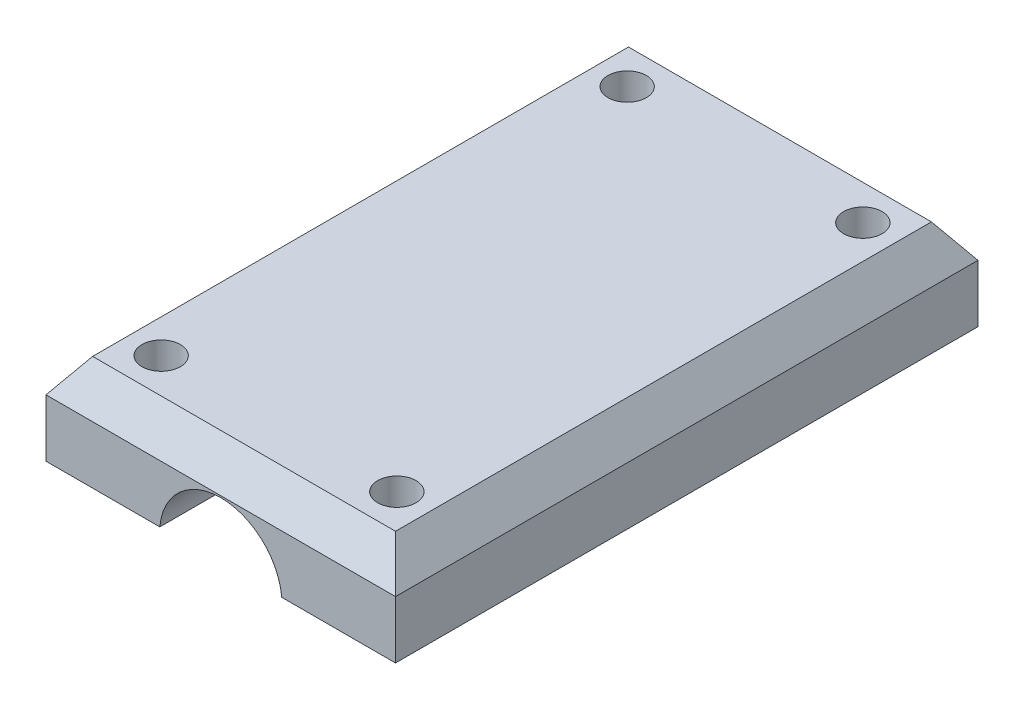
SolidWorks part; units mm, degrees
ref_plane "Front Plane" through (0, 0, 0) normal (0, 0, 1) x (1, 0, 0)
ref_plane "Top Plane" through (0, 0, 0) normal (0, 1, 0) x (1, 0, 0)
ref_plane "Right Plane" through (0, 0, 0) normal (1, 0, 0) x (0, 0, -1)
sketch "Sketch2" plane through (0, 0, 0) normal (0, 0, 1) x (1, 0, 0)
  line L0 (15, 0) -> (5.23, 0) construction
  line L1 (5.23, 0) -> (15, 0)
  line L2 (-5.23, 0) -> (-15, 0)
  line L3 (-15, 0) -> (-15, 7.7924)
  line L4 (-15, 7.7924) -> (15, 7.7924)
  line L5 (15, 7.7924) -> (15, 0)
  line L6 (-15, 4.7924) -> (15, 4.7924) construction
  arc A0 (-5.23, 0) -> (5.23, 0) centre (0, 0.4576) ccw construction
  arc A1 (-5.23, 0) -> (5.23, 0) centre (0, 0.4576) ccw construction
  arc A2 (-5.23, 0) -> (5.23, 0) centre (0, -0.4576) cw
  dimension "D1" = 3
extrude "Boss-Extrude1" add sketch "Sketch2" against normal up to surface (50 mm away)
sketch "Sketch3" plane through (0, 0, -50) normal (0, 0, -1) x (-1, 0, 0)
  line L0 (0, -4.5958) -> (0, 4.5958)
sketch "Sketch4" plane through (0, 7.7924, 0) normal (0, 1, 0) x (1, 0, 0)
  line L0 (-10.115, 45) -> (-10.115, 5) construction
  circle A0 centre (-10.115, 45) radius 1.65
  circle A1 centre (-10.115, 5) radius 1.65
  circle A2 centre (10.115, 45) radius 1.65
  circle A3 centre (10.115, 5) radius 1.65
  dimension "D1" = 3.3
  dimension "D2" = 3.3
  dimension "D3" = 3.3
  dimension "D4" = 3.3
extrude "Cut-Extrude1" cut sketch "Sketch4" against normal up to vertex (7.7924 mm away)
chamfer "Chamfer1" distance 2 angle 55 4 edges at (0, 7.7924, 0) (-15, 7.7924, -25) (0, 7.7924, -50) (15, 7.7924, -25)
